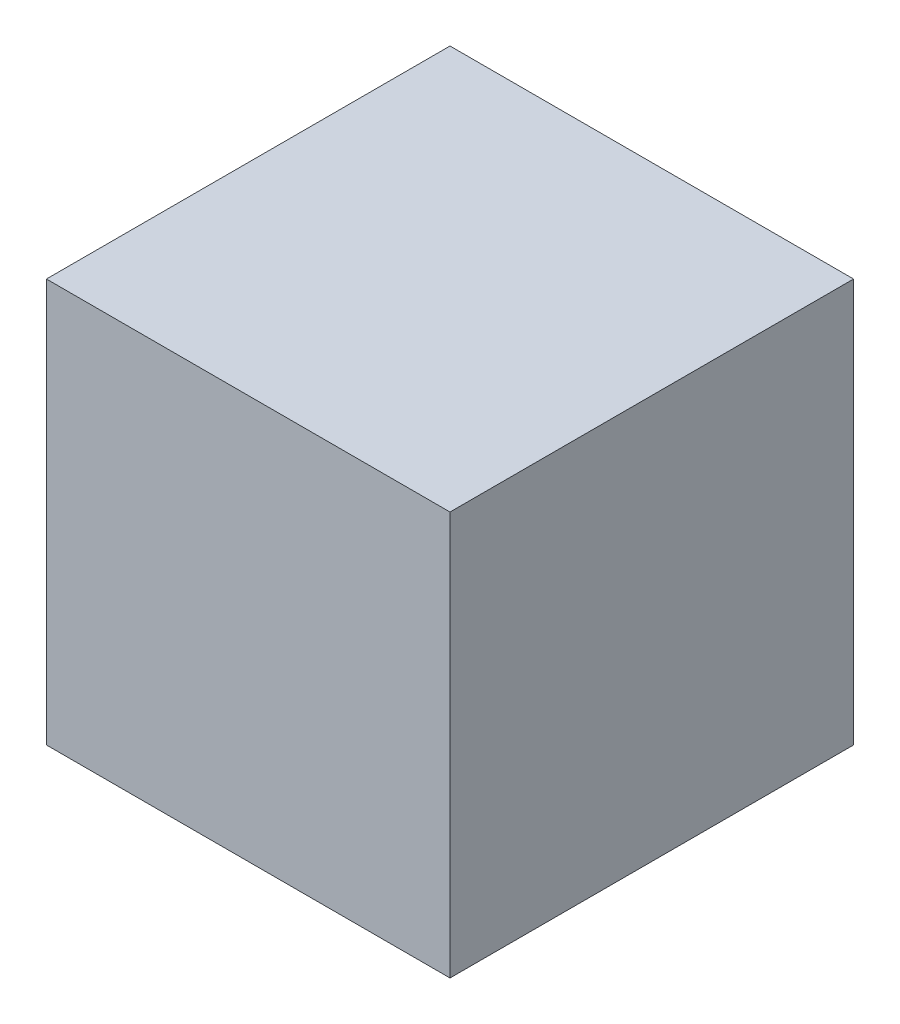
SolidWorks part; units mm, degrees
ref_plane "Front Plane" through (0, 0, 0) normal (0, 0, 1) x (1, 0, 0)
ref_plane "Top Plane" through (0, 0, 0) normal (0, 1, 0) x (1, 0, 0)
ref_plane "Right Plane" through (0, 0, 0) normal (1, 0, 0) x (0, 0, -1)
sketch "Sketch1" plane through (0, 0, 0) normal (0, 0, 1) x (1, 0, 0)
  line L1 (0, 0) -> (28.8, 0)
  line L2 (0, 0) -> (0, 28.8)
  line L3 (0, 28.8) -> (28.8, 28.8)
  line L4 (28.8, 0) -> (28.8, 28.8)
extrude "Boss-Extrude1" add sketch "Sketch1" along normal blind 28.8
